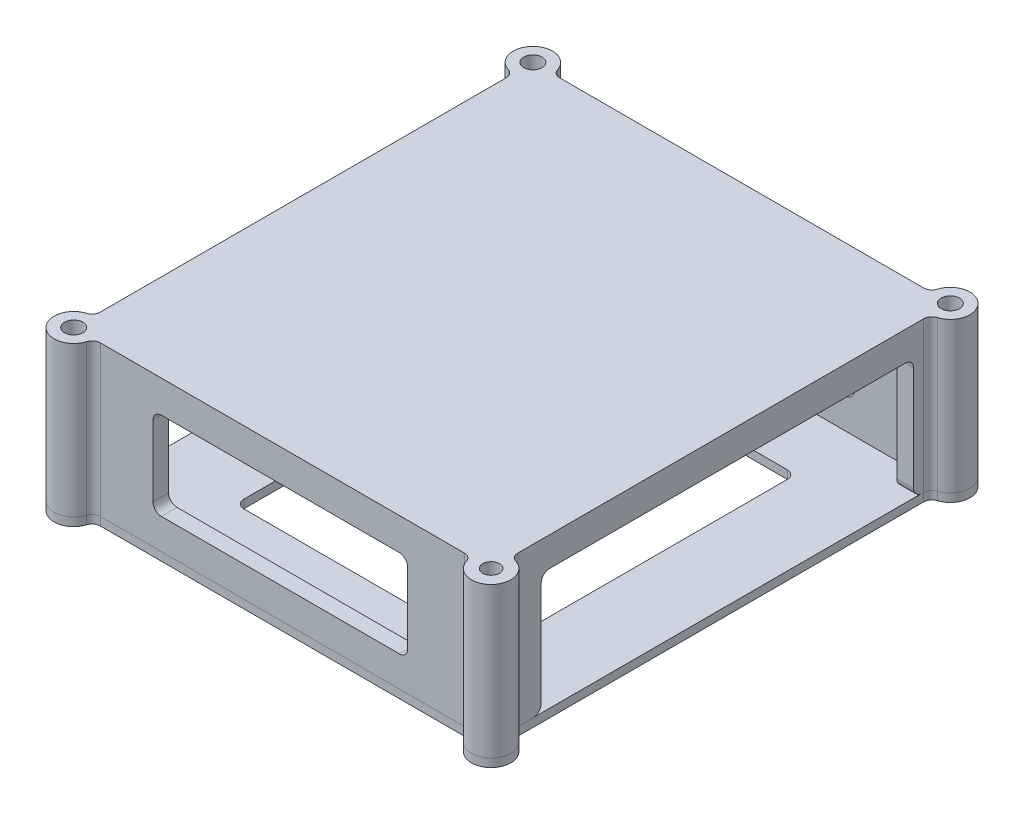
SolidWorks part; units mm, degrees
material "Nylon 101"
ref_plane "Front Plane" through (0, 0, 0) normal (0, 0, 1) x (1, 0, 0)
ref_plane "Top Plane" through (0, 0, 0) normal (0, 1, 0) x (1, 0, 0)
ref_plane "Right Plane" through (0, 0, 0) normal (1, 0, 0) x (0, 0, -1)
sketch "Sketch1" plane through (0, 0, 0) normal (0, 1, 0) x (1, 0, 0)
  line L1 (0, 0) -> (127, 0)
  line L2 (0, 0) -> (0, 139.7)
  line L3 (0, 139.7) -> (127, 139.7)
  line L4 (127, 0) -> (127, 139.7)
  dimension "D1" = 127
  dimension "D2" = 139.7
extrude "Boss-Extrude1" add sketch "Sketch1" along normal blind 45.72
sketch "Sketch3" plane through (0, 0, 0) normal (0, -1, 0) x (1, 0, 0)
  line L0 (0, -139.7) -> (0, 0) construction
  line L1 (6.35, -4.7625) -> (121.92, -4.7625)
  line L2 (6.35, -4.7625) -> (6.35, -135.8265)
  line L3 (6.35, -135.8265) -> (121.92, -135.8265)
  line L4 (121.92, -4.7625) -> (121.92, -135.8265)
  line L5 (0, 0) -> (127, 0) construction
  dimension "D1" = 115.57
  dimension "D2" = 131.064
  dimension "D3" = 6.35
  dimension "D4" = 4.7625
extrude "Cut-Extrude1" cut sketch "Sketch3" against normal blind 44
sketch "Sketch4" plane through (0, 0, -139.7) normal (0, 0, -1) x (-1, 0, 0)
  line L0 (-127, 0) -> (0, 0) construction
  line L1 (-101.6, 35.941) -> (-24.13, 35.941)
  line L2 (-101.6, 35.941) -> (-101.6, 9.271)
  line L3 (-101.6, 9.271) -> (-24.13, 9.271)
  line L4 (-24.13, 35.941) -> (-24.13, 9.271)
  line L7 (-127, 45.72) -> (-127, 0) construction
  dimension "D1" = 26.67
  dimension "D2" = 77.47
  dimension "D3" = 9.271
  dimension "D4" = 25.4
extrude "Cut-Extrude2" cut sketch "Sketch4" against normal blind 190.754
sketch "Sketch5" plane through (127, 0, 0) normal (1, 0, 0) x (0, 0, -1)
  line L0 (0, 45.72) -> (139.7, 45.72) construction
  line L1 (15.24, 36.83) -> (128.524, 36.83)
  line L2 (15.24, 36.83) -> (15.24, -10.16)
  line L3 (15.24, -10.16) -> (128.524, -10.16)
  line L4 (128.524, 36.83) -> (128.524, -10.16)
  line L6 (0, 45.72) -> (0, 0) construction
  dimension "D1" = 46.99
  dimension "D2" = 113.284
  dimension "D3" = 8.89
  dimension "D4" = 15.24
extrude "Cut-Extrude3" cut sketch "Sketch5" against normal blind 190.754 contours L2 L1 L4 L3
sketch "Sketch6" plane through (0, 0, 0) normal (0, -1, 0) x (-1, 0, 0)
  line L7 (-127, 139.7) -> (0, 139.7) construction
  line L8 (-127, 139.7) -> (-127, 0) construction
  line L9 (-127, 0) -> (0, 0) construction
  line L10 (0, 139.7) -> (0, 0) construction
  line L19 (-127, 0) -> (-127, 15.24) construction
  circle A0 centre (0, 0) radius 2.794
  circle A1 centre (-127, 0) radius 2.54
  circle A2 centre (0, 139.7) radius 2.794
  circle A3 centre (-127, 139.7) radius 2.794
  circle A8 centre (0, 139.7) radius 5.969
  circle A9 centre (-127, 139.7) radius 5.969
  circle A10 centre (-127, 0) radius 5.969
  circle A11 centre (0, 0) radius 5.969
  line M2 (-127, 15.24) -> (-127, 0)
  line M3 (-127, 0) -> (0, 0)
  line M4 (0, 0) -> (0, 15.24)
  dimension "D1" = 5.588
  dimension "D2" = 5.08
  dimension "D3" = 5.588
  dimension "D4" = 5.588
  dimension "D6" = 139.7
  dimension "D7" = 3.175
  dimension "D5" = 127
ref_plane "Plane1" through (63.5, 0, 0) normal (1, 0, 0) x (0, 0, -1)
ref_plane "Plane4" through (0, 0, -69.85) normal (0, 0, -1) x (-1, 0, 0)
extrude "Boss-Extrude2" add sketch "Sketch6" against normal through all contours A8 | A11 A0 M3 M4 | A8 A2 | A9 A3 | A10 A1 M2 M3 region at (-2.095, 0, -2.095) region at (131.1013, 0, 4.1013) region at (5.8002, 0, -139.7) region at (132.8002, 0, -139.7)
extrude "Cut-Extrude4" cut sketch "Sketch6<4>" against normal through all contours A0 M3 M4 | A1 M2 M3 | A1 M3 M2 | A0 M4 M3 | A2 | A3 region at (-0.3953, 0, 0.3953) region at (1.1858, 0, -1.1858) region at (125.922, 0, -1.078) region at (127.3593, 0, 0.3593) region at (0, 0, -139.7) region at (127, 0, -139.7)
sketch "Sketch6<4>" plane through (0, 0, 0) normal (0, -1, 0) x (-1, 0, 0) same geometry as "Sketch6"
fillet "Fillet1" radius 2.54 24 edges at (0, 22.86, -133.731) (127, 22.86, -5.969) (24.13, 9.271, -2.3813) (101.6, 9.271, -2.3813) (101.6, 35.941, -2.3813) (24.13, 35.941, -2.3813) (24.13, 9.271, -137.7632) (101.6, 9.271, -137.7632) (101.6, 35.941, -137.7632) (24.13, 35.941, -137.7632) (3.175, 0, -128.524) (3.175, 0, -15.24) (124.46, 0, -15.24) (124.46, 0, -128.524) (3.175, 36.83, -128.524) (124.46, 36.83, -15.24) (3.175, 36.83, -15.24) (124.46, 36.83, -128.524) (121.031, 22.86, 0) (5.969, 22.86, 0) (0, 22.86, -5.969) (121.031, 22.86, -139.7) (127, 22.86, -133.731) (5.969, 22.86, -139.7)
sketch "Sketch7" plane through (0, 0, 0) normal (0, -1, 0) x (1, 0, 0)
  line L49 (127, -131.5789) -> (127, -8.1211)
  line L50 (8.1211, -139.7) -> (118.8789, -139.7)
  line L51 (0, -8.1211) -> (0, -131.5789)
  line L52 (118.8789, 0) -> (8.1211, 0)
  line L53 (127, -131.5789) -> (127, -8.1211)
  line L54 (8.1211, -139.7) -> (118.8789, -139.7)
  line L55 (0, -8.1211) -> (0, -131.5789)
  line L56 (118.8789, 0) -> (8.1211, 0)
  line L59 (25.4, -23.8125) -> (25.4, -116.7765)
  line L60 (25.4, -116.7765) -> (102.87, -116.7765)
  line L61 (102.87, -116.7765) -> (102.87, -23.8125)
  line L62 (102.87, -23.8125) -> (25.4, -23.8125)
  line L63 (25.4, -23.8125) -> (25.4, -116.7765)
  line L64 (25.4, -116.7765) -> (102.87, -116.7765)
  line L65 (102.87, -116.7765) -> (102.87, -23.8125)
  line L66 (102.87, -23.8125) -> (25.4, -23.8125)
  circle A32 centre (127, 0) radius 2.54 construction
  circle A33 centre (127, 0) radius 2.54
  circle A34 centre (127, -139.7) radius 2.794 construction
  circle A35 centre (127, -139.7) radius 2.794
  circle A36 centre (0, 0) radius 2.794 construction
  circle A37 centre (0, -139.7) radius 2.794 construction
  circle A38 centre (0, 0) radius 2.794
  circle A39 centre (0, -139.7) radius 2.794
  arc A44 (128.7818, -5.6969) -> (121.3031, 1.7818) centre (127, 0) ccw
  arc A45 (128.7818, -5.6969) -> (127, -8.1211) centre (129.54, -8.1211) ccw
  arc A46 (127, -131.5789) -> (128.7818, -134.0031) centre (129.54, -131.5789) ccw
  arc A47 (121.3031, -141.4818) -> (128.7818, -134.0031) centre (127, -139.7) ccw
  arc A48 (121.3031, -141.4818) -> (118.8789, -139.7) centre (118.8789, -142.24) ccw
  arc A49 (8.1211, -139.7) -> (5.6969, -141.4818) centre (8.1211, -142.24) ccw
  arc A50 (-1.7818, -134.0031) -> (5.6969, -141.4818) centre (0, -139.7) ccw
  arc A51 (-1.7818, -134.0031) -> (0, -131.5789) centre (-2.54, -131.5789) ccw
  arc A52 (0, -8.1211) -> (-1.7818, -5.6969) centre (-2.54, -8.1211) ccw
  arc A53 (5.6969, 1.7818) -> (-1.7818, -5.6969) centre (0, 0) ccw
  arc A54 (5.6969, 1.7818) -> (8.1211, 0) centre (8.1211, 2.54) ccw
  arc A55 (118.8789, 0) -> (121.3031, 1.7818) centre (118.8789, 2.54) ccw
  arc A56 (128.7818, -5.6969) -> (121.3031, 1.7818) centre (127, 0) ccw
  arc A57 (128.7818, -5.6969) -> (127, -8.1211) centre (129.54, -8.1211) ccw
  arc A58 (127, -131.5789) -> (128.7818, -134.0031) centre (129.54, -131.5789) ccw
  arc A59 (121.3031, -141.4818) -> (128.7818, -134.0031) centre (127, -139.7) ccw
  arc A60 (121.3031, -141.4818) -> (118.8789, -139.7) centre (118.8789, -142.24) ccw
  arc A61 (8.1211, -139.7) -> (5.6969, -141.4818) centre (8.1211, -142.24) ccw
  arc A62 (-1.7818, -134.0031) -> (5.6969, -141.4818) centre (0, -139.7) ccw
  arc A63 (-1.7818, -134.0031) -> (0, -131.5789) centre (-2.54, -131.5789) ccw
  arc A64 (0, -8.1211) -> (-1.7818, -5.6969) centre (-2.54, -8.1211) ccw
  arc A65 (5.6969, 1.7818) -> (-1.7818, -5.6969) centre (0, 0) ccw
  arc A66 (5.6969, 1.7818) -> (8.1211, 0) centre (8.1211, 2.54) ccw
  arc A67 (118.8789, 0) -> (121.3031, 1.7818) centre (118.8789, 2.54) ccw
  dimension "D1" = 0
  dimension "D2" = 19.05
extrude "Boss-Extrude3" add sketch "Sketch7" along normal blind 2.54 separate body
fillet "Fillet2" radius 2.54 4 edges at (25.4, -1.27, -116.7765) (102.87, -1.27, -116.7765) (25.4, -1.27, -23.8125) (102.87, -1.27, -23.8125)
